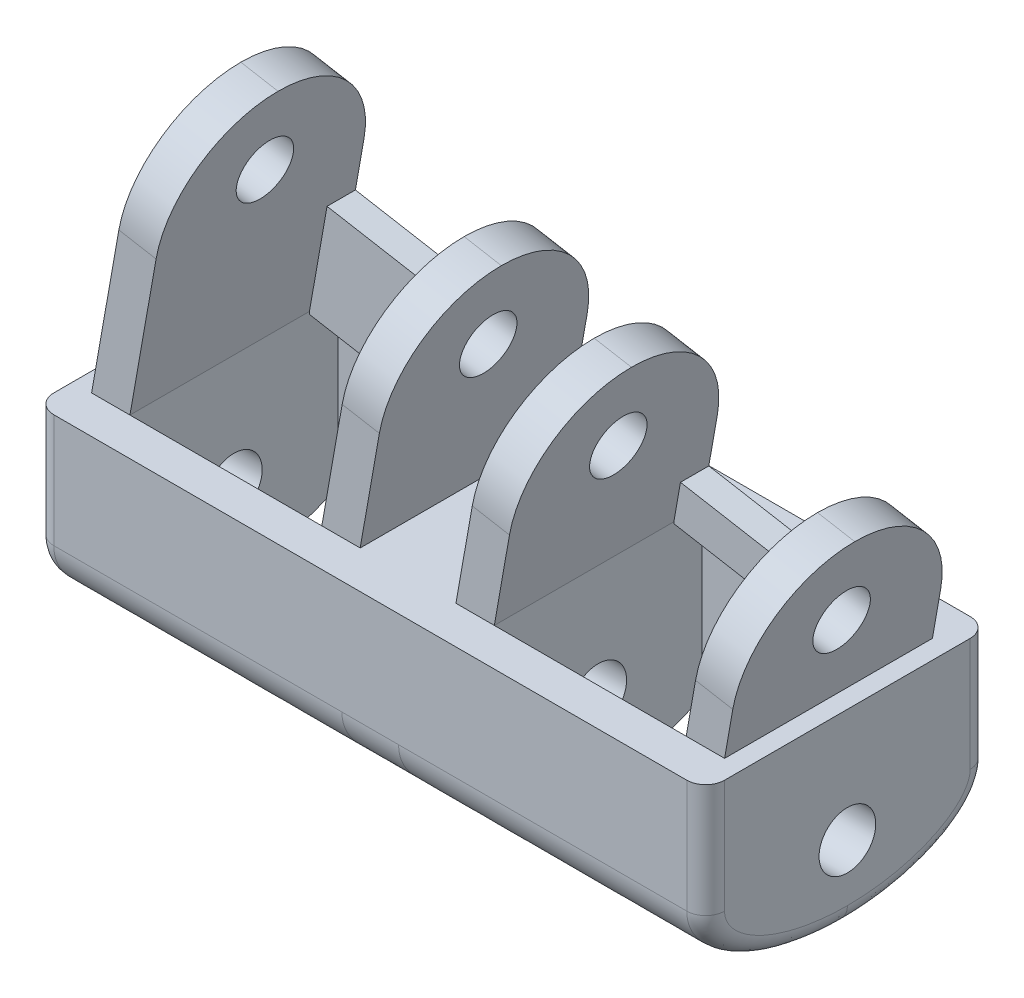
SolidWorks part; units mm, degrees
material "ABS"
ref_plane "Front Plane" through (0, 0, 0) normal (0, 0, 1) x (1, 0, 0)
ref_plane "Top Plane" through (0, 0, 0) normal (0, 1, 0) x (1, 0, 0)
ref_plane "Right Plane" through (0, 0, 0) normal (1, 0, 0) x (0, 0, -1)
sketch "Sketch1" plane through (0, 0, 0) normal (0, 1, 0) x (1, 0, 0)
  line L1 (8.125, 7.5) -> (-8.125, 7.5)
  line L2 (8.125, 7.5) -> (8.125, -7.5)
  line L3 (8.125, -7.5) -> (-8.125, -7.5)
  line L4 (-8.125, 7.5) -> (-8.125, -7.5)
  line L5 (8.125, 7.5) -> (-8.125, -7.5) construction
  line L6 (8.125, -7.5) -> (-8.125, 7.5) construction
  point P0 (0, 0)
  dimension "D1" = 16.25
  dimension "D2" = 15
extrude "Boss-Extrude1" add sketch "Sketch1" along normal blind 10
ref_plane "Plane1" through (-9.625, 0, 0) normal (1, 0, 0) x (0, 0, -1)
fillet "Fillet1" radius 7.5 2 edges at (0, 0, -7.5) (0, 0, 7.5) second distance 4 first distance on face at (0, 0, 0)
sketch "Sketch2" plane through (8.125, 0, 0) normal (1, 0, 0) x (0, 0, -1)
  circle A0 centre (0, 4) radius 1.5
  dimension "D2" = 3
  dimension "D1" = 4
extrude "Cut-Extrude1" cut sketch "Sketch2" against normal through all
mirror "Mirror2" about plane through (-9.625, 0, 0) normal (1, 0, 0) of bodies 102
ref_plane "Plane2" through (0, 0, 5.5) normal (0, 0, 1) x (1, 0, 0)
sketch "Sketch3" plane through (0, 0, 5.5) normal (0, 0, 1) x (1, 0, 0)
  line L0 (7.125, 10) -> (8.5142, 17.8785)
  line L1 (8.5142, 17.8785) -> (6.5446, 18.2258)
  line L2 (6.5446, 18.2258) -> (5.0941, 10)
  line L3 (5.0941, 10) -> (7.125, 10)
  line L4 (-5.0601, 10) -> (-3.3035, 19.9622)
  line L5 (-3.3035, 19.9622) -> (-5.2731, 20.3095)
  line L6 (-5.2731, 20.3095) -> (-7.091, 10)
  line L7 (-7.091, 10) -> (-5.0601, 10)
  line L8 (-5.2731, 20.3095) -> (-32.5662, 25.122) construction
  line L9 (-26.375, 10) -> (-23.9757, 23.6073)
  line L10 (-23.9757, 23.6073) -> (-22.0061, 23.26)
  line L11 (-22.0061, 23.26) -> (-24.3441, 10)
  line L12 (-24.3441, 10) -> (-26.375, 10)
  line L13 (-12.158, 21.5235) -> (-10.1884, 21.1762)
  line L14 (-10.1884, 21.1762) -> (-12.159, 10)
  line L15 (-12.159, 10) -> (-14.1899, 10)
  line L16 (-14.1899, 10) -> (-12.158, 21.5235)
  line L17 (-8.125, 10) -> (8.125, 10) construction
  line L18 (-8.125, 10) -> (8.125, 10) construction
  line L19 (-11.125, 10) -> (-27.375, 10) construction
  line L20 (-11.125, 10) -> (-27.375, 10) construction
  dimension "D1" = 2
  dimension "D2" = 8
  dimension "D3" = 2
  dimension "D4" = 10
  dimension "D5" = 10
  dimension "D6" = 2
  dimension "D7" = 2
  dimension "D8" = 80
  dimension "D9" = 1
  dimension "D10" = 1
extrude "Boss-Extrude2" add sketch "Sketch3" against normal blind 11
sketch "Sketch4" plane through (5.2001, -0.9169, 0) normal (0.9848, -0.1736, 0) x (0, 0, -1)
  line L1 (0, 19.0853) -> (0, 15.0853) construction
  line L2 (5.5, 19.0853) -> (-5.5, 19.0853) construction
  circle A0 centre (0, 15.0853) radius 1.5
  dimension "D2" = 3
  dimension "D1" = 4
extrude "Cut-Extrude2" cut sketch "Sketch4" against normal through all
fillet "Fillet2" radius 5.5 4 edges at (-4.2883, 20.1359, 5.5) (-4.2883, 20.1359, -5.5) (7.5294, 18.0521, -5.5) (7.5294, 18.0521, 5.5)
fillet "Fillet3" radius 5.5 4 edges at (-22.9909, 23.4337, 5.5) (-22.9909, 23.4337, -5.5) (-11.1732, 21.3499, -5.5) (-11.1732, 21.3499, 5.5)
sketch "Sketch5" plane through (-8.125, 0, 0) normal (-1, 0, 0) x (0, 0, 1)
  line L3 (-7.5, 10) -> (-7.5, 4)
  line L4 (7.5, 4) -> (7.5, 10)
  line L5 (7.5, 10) -> (-7.5, 10)
  line L6 (-7.5, 10) -> (-7.5, 4)
  line L7 (7.5, 4) -> (7.5, 10)
  line L8 (7.5, 10) -> (-7.5, 10)
  circle A0 centre (0, 4) radius 1.5 construction
  circle A1 centre (0, 4) radius 1.5
  spline S2 degree 2 poles (2973.0865, 338.2682) (-37.2259, 58.1584) (-7.2035, 2.8865) (-6.946, 2.4123) (-6.4789, 1.985) (-5.7167, 1.2878) (-4.5059, 0.8024) (-3.4942, 0.3968) (-2.2877, 0.1906) (133.6638, -23.0394) (1107.6473, 2784.5073) knots -12.533638 -12.533638 -12.533638 0.125 0.125 0.25 0.25 0.5 0.5 0.75 0.75 31.214562 31.214562 31.214562 only from (-7.5, 4) to (0, 0)
  spline S3 degree 2 poles (-1091.5146, 2790.883) (-133.9015, -23.0436) (2.2856, 0.1903) (3.4883, 0.3955) (4.4997, 0.7999) (5.7125, 1.2849) (6.4775, 1.9838) (6.9446, 2.4104) (7.2032, 2.8859) (37.237, 58.0919) (-2971.934, 349.0394) knots -30.278333 -30.278333 -30.278333 0.25 0.25 0.5 0.5 0.75 0.75 0.875 0.875 13.52409 13.52409 13.52409 only from (0, 0) to (7.5, 4)
  spline S4 degree 2 poles (-7.5, 4) (-7.5, 3.4323) (-7.2035, 2.8865) (-6.946, 2.4123) (-6.4789, 1.985) (-5.7167, 1.2878) (-4.5059, 0.8024) (-3.4942, 0.3968) (-2.2877, 0.1906) (-1.1721, 0) (0, 0) knots 0 0 0 0.125 0.125 0.25 0.25 0.5 0.5 0.75 0.75 1 1 1
  spline S5 degree 2 poles (0, 0) (1.1703, 0) (2.2856, 0.1903) (3.4883, 0.3955) (4.4997, 0.7999) (5.7125, 1.2849) (6.4775, 1.9838) (6.9446, 2.4104) (7.2032, 2.8859) (7.5, 3.4314) (7.5, 4) knots 0 0 0 0.25 0.25 0.5 0.5 0.75 0.75 0.875 0.875 1 1 1
  dimension "D1" = 0
extrude "Boss-Extrude4" add sketch "Sketch5" along normal up to surface (3 mm away) up to face at (-11.125, 4, -1.5)
sketch "Sketch6" plane through (0, 10, 0) normal (0, 1, 0) x (1, 0, 0)
  line L1 (-5.0601, 5.5) -> (5.0941, 5.5)
  line L2 (-5.0601, 5.5) -> (-5.0601, -5.5)
  line L3 (-5.0601, -5.5) -> (5.0941, -5.5)
  line L4 (5.0941, 5.5) -> (5.0941, -5.5)
  line L5 (-24.3441, 5.5) -> (-14.1899, 5.5)
  line L6 (-24.3441, 5.5) -> (-24.3441, -5.5)
  line L7 (-24.3441, -5.5) -> (-14.1899, -5.5)
  line L8 (-14.1899, 5.5) -> (-14.1899, -5.5)
extrude "Cut-Extrude3" cut sketch "Sketch6" against normal through all
sketch "Sketch7" plane through (-6.6176, 1.1669, 0) normal (0.9848, -0.1736, 0) x (0, 0, -1)
  line L0 (5.5, 8.9694) -> (5.5, 13.5853) construction
  line L1 (5.5, 10.9853) -> (4, 10.9853)
  line L2 (5.5, 10.9853) -> (5.5, 8.8853)
  line L3 (5.5, 8.8853) -> (4, 8.8853)
  line L4 (4, 10.9853) -> (4, 8.8853)
  dimension "D1" = 2.6
  dimension "D2" = 2.1
  dimension "D3" = 1.5
extrude "Boss-Extrude5" add sketch "Sketch7" along normal up to next
sketch "Sketch8" plane through (-25.3202, 4.4646, 0) normal (0.9848, -0.1736, 0) x (0, 0, -1)
  line L0 (5.5, 5.6208) -> (5.5, 13.5853) construction
  line L1 (5.5, 10.9853) -> (4, 10.9853)
  line L2 (5.5, 10.9853) -> (5.5, 5.4853)
  line L3 (5.5, 5.4853) -> (4, 5.4853)
  line L4 (4, 10.9853) -> (4, 5.4853)
  dimension "D1" = 2.6
  dimension "D2" = 5.5
  dimension "D3" = 1.5
extrude "Boss-Extrude6" add sketch "Sketch8" along normal up to next contours L1 L4 L3 L2
fillet "Fillet4" radius 1 8 edges
